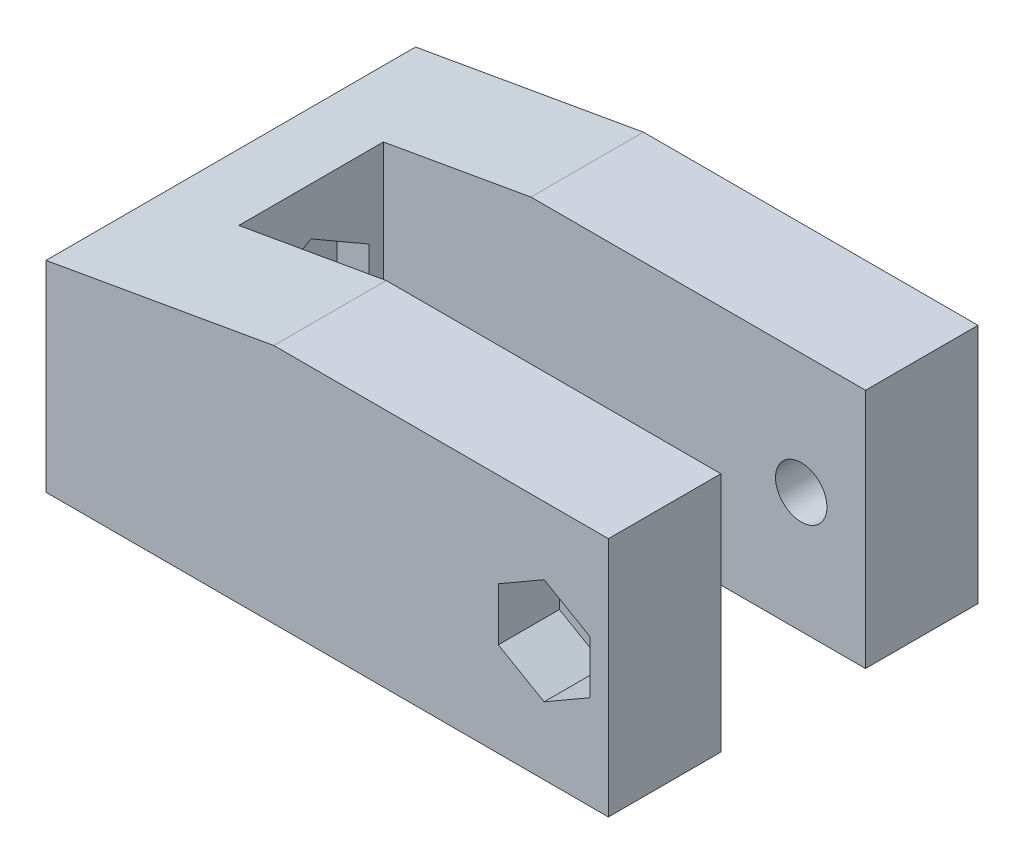
SolidWorks part; units mm, degrees
ref_plane "Front Plane" through (0, 0, 0) normal (0, 0, 1) x (1, 0, 0)
ref_plane "Top Plane" through (0, 0, 0) normal (0, 1, 0) x (1, 0, 0)
ref_plane "Right Plane" through (0, 0, 0) normal (1, 0, 0) x (0, 0, -1)
sketch "Sketch1" plane through (0, 0, 0) normal (1, 0, 0) x (0, 0, -1)
  line L1 (0, 0) -> (23, 0)
  line L2 (0, 0) -> (0, 15)
  line L3 (0, 15) -> (23, 15)
  line L4 (23, 0) -> (23, 15)
  dimension "D1" = 23
  dimension "D2" = 15
extrude "Boss-Extrude1" add sketch "Sketch1" along normal blind 35
sketch "Sketch2" plane through (35, 0, 0) normal (1, 0, 0) x (0, 0, -1)
  line L0 (11.5, 15) -> (11.5, 0) construction
  line L1 (7, 15) -> (16, 15)
  line L2 (7, 15) -> (7, 0)
  line L3 (7, 0) -> (16, 0)
  line L4 (16, 15) -> (16, 0)
  line L5 (0, 0) -> (23, 0) construction
  line L8 (23, 15) -> (0, 15) construction
  line L9 (11.5, 15) -> (11.5, 0) construction
  dimension "D1" = 9
extrude "Cut-Extrude1" cut sketch "Sketch2" against normal offset from surface (30 mm away) 5 up to face at (0, 7.5, -11.5)
sketch "Sketch3" plane through (0, 0, -23) normal (0, 0, -1) x (-1, 0, 0)
  line L1 (-35, 0) -> (-35, 15) construction
  line L2 (-35, 0) -> (0, 0) construction
  circle A0 centre (-31, 7.5) radius 1.6
  dimension "D3" = 3.2
  dimension "D1" = 7.5
  dimension "D2" = 4
extrude "Cut-Extrude2" cut sketch "Sketch3" against normal through all both and the other way through all
chamfer "Chamfer1" distance 2.5 angle 80 1 edges at (0, 15, -11.5) first distance on face at (0, 7.5, -11.5)
sketch "Sketch4" plane through (0, 0, 0) normal (-1, 0, 0) x (0, 0, 1)
  line L0 (-11.5, 12.5) -> (-11.5, 0) construction
  line L1 (0, 12.5) -> (-23, 12.5) construction
  line L2 (0, 0) -> (-23, 0) construction
  line L3 (-23, 6.25) -> (0, 6.25) construction
  line L4 (-23, 0) -> (-23, 12.5) construction
  line L5 (0, 12.5) -> (0, 0) construction
  circle A0 centre (-11.5, 6.25) radius 2.2
  dimension "D1" = 4.4
extrude "Cut-Extrude3" cut sketch "Sketch4" against normal blind 10
sketch "Sketch5" plane through (5, 0, 0) normal (1, 0, 0) x (0, 0, -1)
  line L1 (7.9, 8.3285) -> (7.9, 4.1715)
  line L2 (7.9, 4.1715) -> (11.5, 2.0931)
  line L3 (11.5, 2.0931) -> (15.1, 4.1715)
  line L4 (15.1, 4.1715) -> (15.1, 8.3285)
  line L5 (15.1, 8.3285) -> (11.5, 10.4069)
  line L6 (11.5, 10.4069) -> (7.9, 8.3285)
  circle A0 centre (11.5, 6.25) radius 3.6 construction
  dimension "D1" = 7.2
extrude "Cut-Extrude4" cut sketch "Sketch5" against normal blind 2
sketch "Sketch6" plane through (0, 0, -23) normal (0, 0, -1) x (-1, 0, 0)
  circle A0 centre (-31, 7.5) radius 3.25
  dimension "D1" = 6.5
extrude "Cut-Extrude5" cut sketch "Sketch6" against normal blind 2.5
sketch "Sketch7" plane through (0, 0, 0) normal (0, 0, 1) x (1, 0, 0)
  line L1 (28.15, 9.1454) -> (28.15, 5.8546)
  line L2 (28.15, 5.8546) -> (31, 4.2091)
  line L3 (31, 4.2091) -> (33.85, 5.8546)
  line L4 (33.85, 5.8546) -> (33.85, 9.1454)
  line L5 (33.85, 9.1454) -> (31, 10.7909)
  line L6 (31, 10.7909) -> (28.15, 9.1454)
  circle A0 centre (31, 7.5) radius 2.85 construction
  dimension "D1" = 5.7
extrude "Cut-Extrude6" cut sketch "Sketch7" against normal blind 3.8
